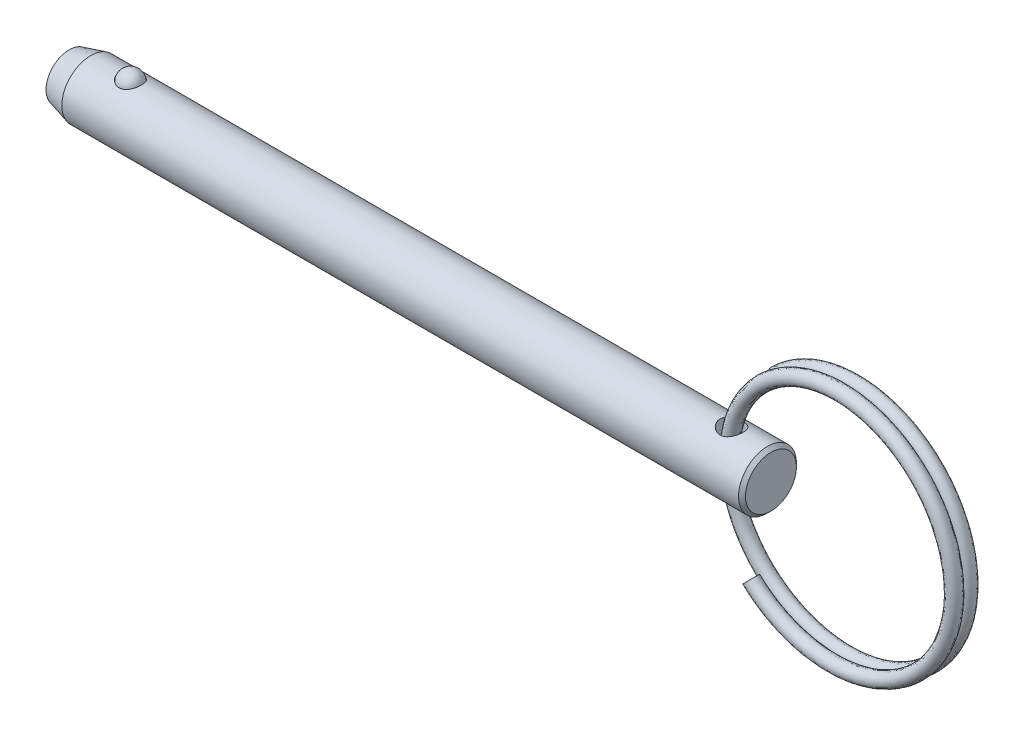
SolidWorks part; units mm, degrees
material "Plain Carbon Steel"
ref_plane "Front" through (0, 0, 0) normal (0, 0, 1) x (1, 0, 0)
ref_plane "Top" through (0, 0, 0) normal (0, 1, 0) x (1, 0, 0)
ref_plane "Right" through (0, 0, 0) normal (1, 0, 0) x (0, 0, -1)
sketch "Sketch1" plane through (0, 0, 0) normal (0, 0, 1) x (1, 0, 0)
  line L0 (38.5064, 2.794) -> (38.1254, 3.175)
  line L1 (38.1254, 3.175) -> (38.5064, 3.175) construction
  line L4 (38.5064, 2.794) -> (38.5064, 0)
  line L5 (38.5064, 3.175) -> (38.5064, 2.794) construction
  line L16 (38.1254, 3.175) -> (-36.1365, 3.175)
  line L17 (-38.5064, 3.175) -> (-38.5064, 2.54) construction
  line L19 (-36.1365, 3.175) -> (-38.5064, 3.175) construction
  line L22 (-38.5064, -3.175) -> (-36.1365, -3.175) construction
  line L23 (-31.7719, 2.8575) -> (-31.7719, -2.8575) construction
  line L24 (-38.5064, 0) -> (38.5064, 0)
  line L27 (38.5064, 0) -> (41.3004, 0) construction
  line L29 (-38.5064, 0) -> (-38.5064, -2.54) construction
  line L36 (32.9184, 0) -> (32.9184, 3.175) construction
  line L37 (-38.5064, 2.54) -> (-38.5064, 0)
  line L38 (-36.1365, -3.175) -> (38.5064, -3.175) construction
  line L39 (-38.5064, -2.54) -> (-38.5064, -3.175) construction
  line L40 (-36.1365, 3.175) -> (-38.5064, 2.54)
  line L42 (-36.1365, -3.175) -> (-38.5064, -2.54) construction
  line L43 (-36.1365, 3.175) -> (-36.1365, -3.175) construction
  circle A2 centre (-31.7719, 2.8575) radius 1.2319 construction
  point P35 (-30.5816, 3.175)
  dimension "A1" = 15
revolve "Revolve1" add sketch "Sketch1" angle 360 about L27
sketch "Sketch2" plane through (0, 0, 0) normal (0, 0, 1) x (1, 0, 0)
  line L0 (-30.5146, 2.8575) -> (-33.0292, 2.8575)
  line L1 (-31.7719, 4.0894) -> (-31.7719, 4.1148) construction
  line L2 (-30.5146, 2.8575) -> (-28, 2.8575) construction
  circle A0 centre (-31.7719, 2.8575) radius 1.2319 construction
  circle A1 centre (-31.7719, 2.8575) radius 1.2319 construction
  arc A2 (-33.0292, 2.8575) -> (-30.5146, 2.8575) centre (-31.7719, 2.8575) cw
  dimension "D1" = 0.0254
revolve "Cut-Revolve1" cut sketch "Sketch2" angle 360 about L2
sketch "Sketch3" plane through (0, 0, 0) normal (0, 0, 1) x (1, 0, 0)
  line L0 (-30.54, 2.8575) -> (-33.0038, 2.8575)
  line L1 (-30.54, 2.8575) -> (-28.0762, 2.8575) construction
  circle A0 centre (-31.7719, 2.8575) radius 1.2319 construction
  arc A1 (-30.54, 2.8575) -> (-33.0038, 2.8575) centre (-31.7719, 2.8575) ccw
revolve "Revolve2" add sketch "Sketch3" angle 360 about L1
sketch "Sketch4" plane through (0, 0, 0) normal (0, 0, 1) x (1, 0, 0)
  line L1 (34.1884, -3.175) -> (35.4584, -3.175)
  line L2 (34.1884, -3.175) -> (34.1884, 3.175)
  line L3 (34.1884, 3.175) -> (35.4584, 3.175)
  line L4 (35.4584, -3.175) -> (35.4584, 3.175)
  line L5 (34.1884, -3.175) -> (34.1884, -4.445) construction
  line L6 (35.4584, 3.175) -> (38.5064, 3.175) construction
  line L8 (32.9184, -3.175) -> (32.9184, 3.175) construction
  line L9 (32.9184, 0) -> (34.1884, 0) construction
  line L11 (34.1884, 0) -> (35.4584, 0) construction
  line L12 (38.1254, 3.175) -> (-36.1365, 3.175) construction
  line L14 (-36.1365, -3.175) -> (38.5064, -3.175) construction
  dimension "D1" = 2.54
revolve "Cut-Revolve2" cut sketch "Sketch4" angle 360 about L2
sketch "Sketch5" plane through (0, 0, 0) normal (0, 0, 1) x (1, 0, 0)
  line L0 (0, 0) -> (33.2114, 0) construction
  line L1 (33.2114, 0) -> (33.2114, 3.175) construction
  line L2 (38.1254, 3.175) -> (-36.1365, 3.175) construction
  line L3 (46.6734, 0) -> (60.1354, 0) construction
  line L4 (35.4584, 3.175) -> (35.1654, 3.175) construction
  line L5 (34.1884, 3.175) -> (35.4584, 3.175) construction
  line L6 (33.5912, 3.175) -> (33.5912, -3.175) construction
  line L7 (33.2114, 3.175) -> (32.9184, 3.175) construction
  line L8 (34.1884, -3.175) -> (35.4584, -3.175) construction
  line L9 (33.5912, -3.175) -> (35.4584, -3.175) construction
  line L10 (33.2114, 0) -> (46.6734, 0) construction
  line L12 (35.1654, 3.175) -> (33.5912, 3.175) construction
  line L13 (46.6734, 11.938) -> (46.6734, 13.462) construction
  circle A0 centre (46.6734, 0) radius 13.462
  circle A1 centre (46.6734, 0) radius 11.938 construction
  circle A2 centre (46.6734, 0) radius 12.7 construction
  point P26 (46.6734, 12.7)
curve "Helix/Spiral1" pitch 1.5494 height 1.3557 radius 13.462 left hand yes centre (46.6734, 0, 0) axis (0, 0, -1) start towards (1, 0, 0)
sketch "Sketch6" plane through (114.0038, 0, 0) normal (0, 1, 0) x (0, 0, -1)
  line L0 (0, 79.2684) -> (0, 80.0304) construction
  line L1 (0, 80.0304) -> (0, 80.7924) construction
  circle A0 centre (0, 80.0304) radius 0.762
  dimension "D1" = 1.524
sketch "Sketch7" plane through (0, 0, 0) normal (0, 0, 1) x (1, 0, 0)
  circle A0 centre (46.6734, 0) radius 13.462 construction
  circle A1 centre (46.6734, 0) radius 13.462
curve "Helix/Spiral2" pitch 1.5494 height 1.3557 radius 13.462 left hand yes centre (46.6734, 0, 0) axis (0, 0, 1) start towards (1, 0, 0)
sweep "Sweep1" add profiles "Sketch6" path "Helix/Spiral1"
sweep "Sweep2" add profiles "Sketch6<2>" path "Helix/Spiral2"
sketch "Sketch6<2>" plane through (114.0038, 0, 0) normal (0, 1, 0) x (0, 0, -1) same geometry as "Sketch6"
equation "\"D12@Sketch1\"=\"A@Sketch1\" * 0.80"
equation "\"D2@Sketch1\"=\"A@Sketch1\" * 0.9"
equation "\"D1@Sketch4\" = \"A@Sketch1\" / 2.5"
equation "\"Ring OD@Sketch5\" = \"R Ring Dia@Sketch5\" * 0.06"
equation "\"D4@Helix/Spiral1\"=\"Ring OD@Sketch5\" + 0.001"
equation "\"D1@Sketch6\"=\"Ring OD@Sketch5\""
equation "\"D4@Helix/Spiral2\" = \"D4@Helix/Spiral1\""
equation "\"D5@Helix/Spiral2\" = \"D5@Helix/Spiral1\""
